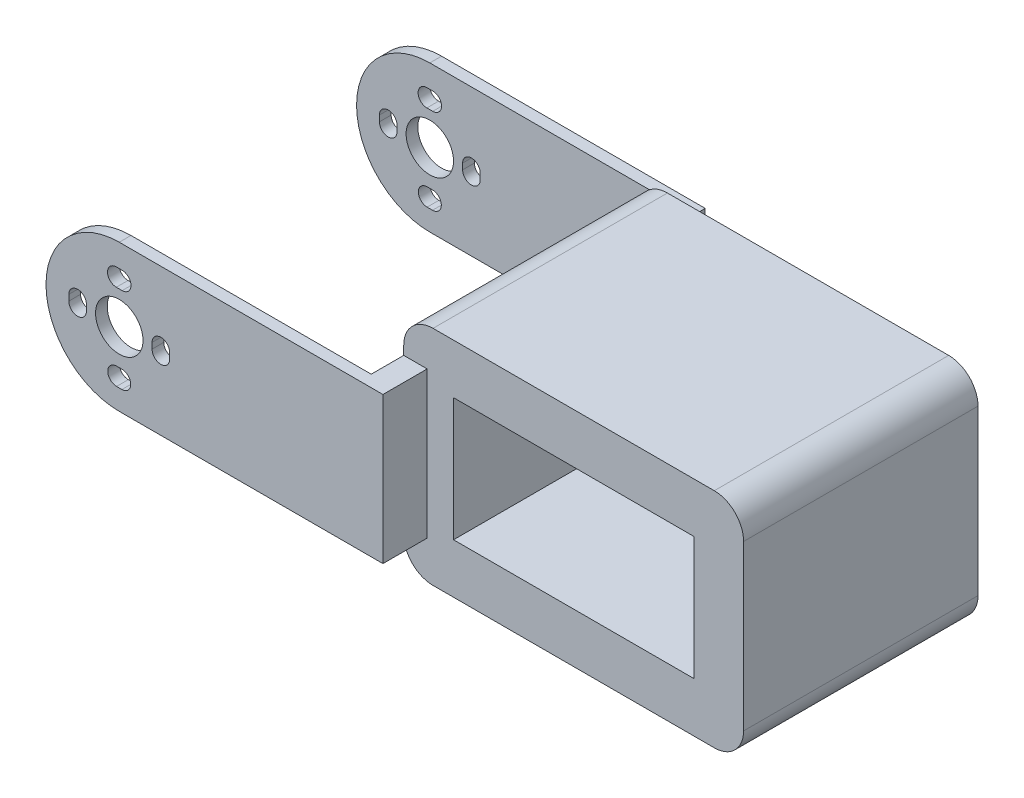
SolidWorks part; units mm, degrees
ref_plane "前基準面" through (0, 0, 0) normal (0, 0, 1) x (1, 0, 0)
ref_plane "上基準面" through (0, 0, 0) normal (0, 1, 0) x (1, 0, 0)
ref_plane "右基準面" through (0, 0, 0) normal (1, 0, 0) x (0, 0, -1)
sketch "Sketch1" plane through (0, 0, 0) normal (0, 0, 1) x (1, 0, 0)
  line L0 (-29.0958, -6.1361) -> (28.9042, -6.1361) construction
  line L1 (-20.5958, 4.3639) -> (20.4042, 4.3639)
  line L2 (-20.5958, 4.3639) -> (-20.5958, -16.6361)
  line L3 (-20.5958, -16.6361) -> (20.4042, -16.6361)
  line L4 (20.4042, 4.3639) -> (20.4042, -16.6361)
  line L5 (-29.0958, 12.8639) -> (28.9042, 12.8639)
  line L6 (-29.0958, 12.8639) -> (-29.0958, -25.1361)
  line L7 (-29.0958, -25.1361) -> (28.9042, -25.1361)
  line L8 (28.9042, 12.8639) -> (28.9042, -25.1361)
  line L9 (-0.0958, 12.8639) -> (-0.0958, -25.1361) construction
  line L10 (20.4042, -6.1361) -> (-20.5958, -6.1361) construction
  line L11 (-0.0958, 4.3639) -> (-0.0958, -16.6361) construction
  point P16 (-0.0958, -6.1361)
  point P17 (-0.0958, -6.1361)
  dimension "D1" = 21
  dimension "D2" = 41
  dimension "D3" = 58
  dimension "D4" = 38
extrude "Boss-Extrude1" add sketch "Sketch1" along normal blind 40
sketch "Sketch2" plane through (0, 0, 40) normal (0, 0, 1) x (1, 0, 0)
  line L0 (-20.5958, -6.1361) -> (-29.0958, -6.1361) construction
  line L2 (-20.5958, 4.3639) -> (-20.5958, -16.6361) construction
  line L3 (-29.0958, 12.8639) -> (-29.0958, -25.1361) construction
  line L4 (-25.0958, -6.1361) -> (-29.4032, -6.1361) construction
  line L5 (-29.0958, 6.3639) -> (-25.0958, 6.3639)
  line L6 (-29.0958, 6.3639) -> (-29.0958, -18.6361)
  line L7 (-29.0958, -18.6361) -> (-25.0958, -18.6361)
  line L8 (-25.0958, 6.3639) -> (-25.0958, -18.6361)
  point P13 (-24.8458, -6.1361)
  dimension "D1" = 25
  dimension "D2" = 4
extrude "Boss-Extrude2" add sketch "Sketch2" along normal blind 5.55
extrude "Boss-Extrude3" add sketch "Sketch2<2>" against normal blind 45.55
sketch "Sketch2<2>" plane through (0, 0, 40) normal (0, 0, 1) x (1, 0, 0) same geometry as "Sketch2"
sketch "Sketch3" plane through (0, 0, 45.55) normal (0, 0, 1) x (1, 0, 0)
  line L0 (-70.5958, 0.9639) -> (-69.5958, 0.9639) construction
  line L1 (-25.0958, 6.3639) -> (-70.0958, 6.3639)
  line L2 (-25.0958, 6.3639) -> (-25.0958, -18.6361)
  line L3 (-25.0958, -18.6361) -> (-70.0958, -18.6361)
  line L4 (-70.0958, 6.3639) -> (-70.0958, -18.6361)
  line L5 (-70.5958, 2.4639) -> (-69.5958, 2.4639)
  line L6 (-70.5958, -0.5361) -> (-69.5958, -0.5361)
  line L7 (-70.0958, 6.3639) -> (-70.0958, -18.6361) construction
  line L8 (-70.5559, -13.6762) -> (-69.6357, -13.6762) construction
  line L9 (-70.5559, -12.1762) -> (-69.6357, -12.1762)
  line L10 (-70.5559, -15.1762) -> (-69.6357, -15.1762)
  line L11 (-70.0958, -6.1361) -> (-82.5958, -6.1361) construction
  line L12 (-77.1958, -5.6361) -> (-77.1958, -6.6361) construction
  line L15 (-75.6958, -5.6361) -> (-75.6958, -6.6361)
  line L16 (-78.6958, -5.6361) -> (-78.6958, -6.6361)
  line L17 (-62.9958, -5.6361) -> (-62.9958, -6.6361) construction
  line L18 (-61.4958, -5.6361) -> (-61.4958, -6.6361)
  line L19 (-64.4958, -5.6361) -> (-64.4958, -6.6361)
  line L20 (-70.0958, -6.1361) -> (-25.0958, -6.1361) construction
  arc A0 (-70.0958, 6.3639) -> (-70.0958, -18.6361) centre (-70.0958, -6.1361) ccw
  circle A1 centre (-70.0958, -6.1361) radius 4.05
  arc A3 (-70.5958, 2.4639) -> (-70.5958, -0.5361) centre (-70.5958, 0.9639) ccw
  arc A4 (-69.5958, -0.5361) -> (-69.5958, 2.4639) centre (-69.5958, 0.9639) ccw
  arc A5 (-70.5559, -12.1762) -> (-70.5559, -15.1762) centre (-70.5559, -13.6762) ccw
  arc A6 (-69.6357, -15.1762) -> (-69.6357, -12.1762) centre (-69.6357, -13.6762) ccw
  arc A9 (-75.6958, -5.6361) -> (-78.6958, -5.6361) centre (-77.1958, -5.6361) ccw
  arc A10 (-78.6958, -6.6361) -> (-75.6958, -6.6361) centre (-77.1958, -6.6361) ccw
  arc A11 (-61.4958, -5.6361) -> (-64.4958, -5.6361) centre (-62.9958, -5.6361) ccw
  arc A12 (-64.4958, -6.6361) -> (-61.4958, -6.6361) centre (-62.9958, -6.6361) ccw
  point P9 (-70.0958, 0.9639)
  point P14 (-68.0958, 0.9639)
  point P15 (-72.0958, 0.9639)
  point P19 (-70.0958, -13.6762)
  point P25 (-77.1958, -6.1361)
  point P31 (-77.1958, -4.1361)
  point P32 (-77.1958, -8.1361)
  point P33 (-43.4958, -6.1361)
  point P34 (-75.6958, -6.1361)
  point P37 (-62.9958, -6.1361)
  point P42 (-62.9958, -4.1361)
  point P43 (-62.9958, -8.1361)
  line M15 (-29.0958, 6.3639) -> (-29.0958, -18.6361)
  line M16 (-29.0958, -18.6361) -> (-25.0958, -18.6361)
  line M17 (-25.0958, -18.6361) -> (-25.0958, 6.3639)
  line M18 (-25.0958, 6.3639) -> (-29.0958, 6.3639)
  dimension "D2" = 4
  dimension "D10" = 5.6
  dimension "D9" = 4
  dimension "D1" = 45
  dimension "D3" = 3
  dimension "D4" = 5.6
  dimension "D5" = 25
  dimension "D6" = 6.0402
  dimension "D7" = 0
  dimension "D8" = 3
  dimension "D11" = 5.6
  dimension "D12" = 3
  dimension "D13" = 4
extrude "Boss-Extrude6" add sketch "Sketch3" along normal blind 2 contours A5 L9 L4 A1 L6 A3 L5 A0 L10 A10 L16 A9 L15 | A6 L10 L4 L3 L1 L5 A4 L6 A1 L9 A12 L19 A11 L18 M15 | M18 M15 M16 M17 region at (-27.0958, -6.1361, 45.55) region at (-48.7644, -6.1347, 45.55) region at (-70.3753, 4.4139, 45.55)
extrude "Boss-Extrude7" add sketch "Sketch3<8>" against normal blind 53 contours A5 L9 L4 A1 L6 A3 L5 A0 L10 A10 L16 A9 L15 | A6 L10 L4 L3 L1 L5 A4 L6 A1 L9 A12 L19 A11 L18 M15 | M18 M15 M16 M17 region at (-27.0958, -6.1361, 45.55) region at (-48.7644, -6.1347, 45.55) region at (-70.3753, 4.4139, 45.55)
sketch "Sketch3<8>" plane through (0, 0, 45.55) normal (0, 0, 1) x (1, 0, 0) same geometry as "Sketch3"
extrude "Cut-Extrude1" cut sketch "Sketch3<11>" against normal blind 51 contours A6 L10 L4 L3 L1 L5 A4 L6 A1 L9 A12 L19 A11 L18 M15 | A5 L9 L4 A1 L6 A3 L5 A0 L10 A10 L16 A9 L15 region at (-48.7644, -6.1347, 45.55) region at (-70.3753, 4.4139, 45.55)
sketch "Sketch3<11>" plane through (0, 0, 45.55) normal (0, 0, 1) x (1, 0, 0) same geometry as "Sketch3"
fillet "Fillet2" radius 5 1 edges at (28.9042, 12.8639, 20) type face fillet first side face at (-0.0958, 12.8639, 20) second side face at (28.9042, -6.1361, 20)
fillet "Fillet3" radius 5 1 edges at (28.9042, -25.1361, 20) type face fillet first side face at (28.9042, -8.6361, 20) second side face at (-0.0958, -25.1361, 20)
fillet "Fillet4" radius 5 1 edges at (-29.0958, 12.8639, 20) type face fillet first side face at (-29.0958, -6.1361, 20.0167) second side face at (-2.5958, 12.8639, 20)
fillet "Fillet5" radius 5 1 edges at (-29.0958, -25.1361, 20) type face fillet first side face at (-2.5958, -25.1361, 20) second side face at (-29.0958, -6.9694, 20.0167)
